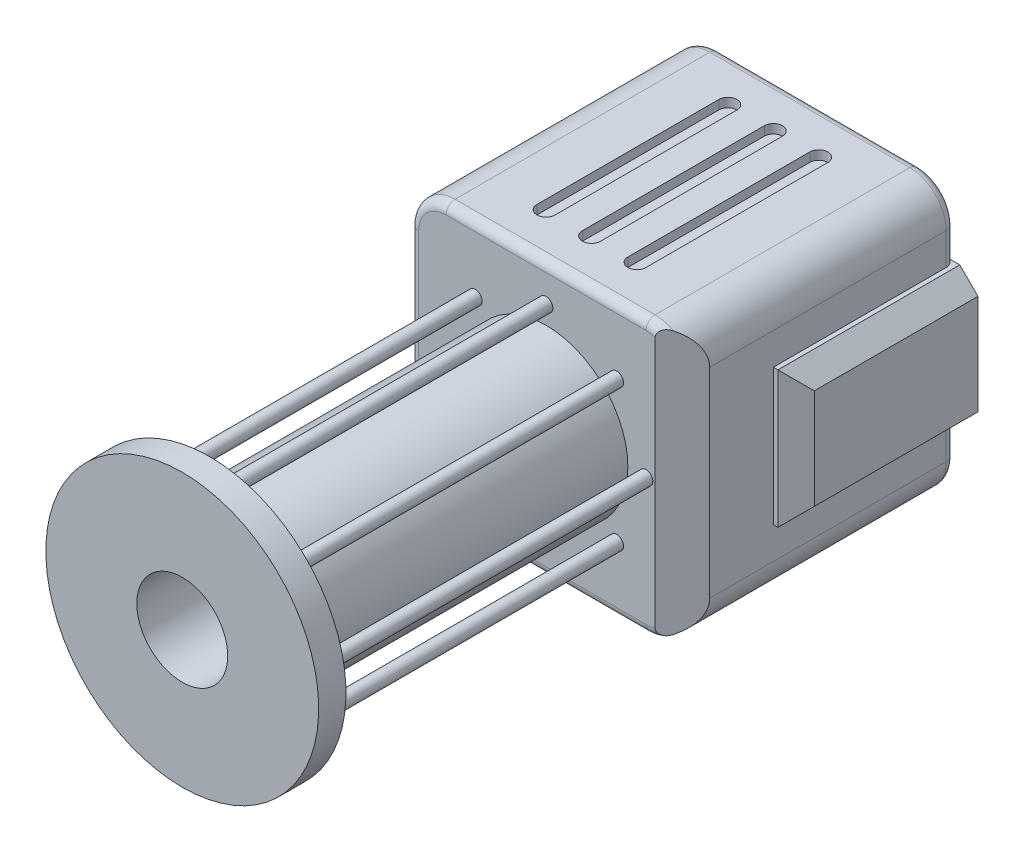
SolidWorks part; units mm, degrees
ref_plane "Front Plane" through (0, 0, 0) normal (0, 0, 1) x (1, 0, 0)
ref_plane "Top Plane" through (0, 0, 0) normal (0, 1, 0) x (1, 0, 0)
ref_plane "Right Plane" through (0, 0, 0) normal (1, 0, 0) x (0, 0, -1)
sketch "Sketch1" plane through (0, 0, 0) normal (0, 0, 1) x (1, 0, 0)
  line L1 (-15, 15) -> (15, 15)
  line L2 (-15, 15) -> (-15, -15)
  line L3 (-15, -15) -> (15, -15)
  line L4 (15, 15) -> (15, -15)
  line L5 (-15, 15) -> (15, -15) construction
  line L6 (-15, -15) -> (15, 15) construction
  point P0 (0, 0)
  dimension "D1" = 30
  dimension "D2" = 30
extrude "Boss-Extrude1" add sketch "Sketch1" along normal mid plane 30
sketch "Sketch2" plane through (0, 0, 0) normal (1, 0, 0) x (0, 0, -1)
  line L0 (-15, 0) -> (-55, 0) construction
  line L1 (-15, -15) -> (-15, 15) construction
  line L2 (-55, 0) -> (-55, 15)
  line L3 (-55, 15) -> (-52, 15)
  line L4 (-52, 15) -> (-52, 9)
  line L5 (-52, 9) -> (-15, 9)
  line L6 (-15, 9) -> (-15, 0)
  line L7 (-15, 0) -> (-55, 0)
  dimension "D1" = 40
  dimension "D2" = 18
  dimension "D3" = 30
  dimension "D4" = 3
revolve "Revolve1" add sketch "Sketch2" angle 360 about L0
fillet "Fillet1" radius 4 4 edges at (-15, 15, 0) (-15, -15, 0) (15, -15, 0) (15, 15, 0)
chamfer "Chamfer2" distance 3 angle 45 1 edges at (15, 0, 15)
fillet "Fillet2" radius 1 15 edges at (13.8284, 13.8284, -15) (15, 0, -15) (13.8284, -13.8284, -15) (0, -15, -15) (-13.8284, -13.8284, -15) (-15, 0, -15) (-13.8284, 13.8284, -15) (11.504, 14.9681, 15) (11.504, -14.9681, 15) (0, -15, 15) (-13.8284, -13.8284, 15) (-15, 0, 15) (-13.8284, 13.8284, 15) (0, 15, -15) (0, 15, 15)
sketch "Sketch3" plane through (0, 0, -15) normal (0, 0, -1) x (-1, 0, 0)
  circle A0 centre (0, 0) radius 10
  dimension "D1" = 20
extrude "Boss-Extrude2" add sketch "Sketch3" along normal mid plane 5
fillet "Fillet3" radius 5 1 edges at (-10, 0, -17.5)
sketch "Sketch5" plane through (0, 0, -15) normal (0, 0, -1) x (-1, 0, 0)
  line L0 (-15, -11) -> (-15, 11) construction
  line L1 (-12.5, -7.5) -> (-17.5, -7.5)
  line L2 (-12.5, -7.5) -> (-12.5, 7.5)
  line L3 (-12.5, 7.5) -> (-17.5, 7.5)
  line L4 (-17.5, -7.5) -> (-17.5, 7.5)
  line L5 (-12.5, -7.5) -> (-17.5, 7.5) construction
  line L6 (-12.5, 7.5) -> (-17.5, -7.5) construction
  point P0 (-15, 0)
  dimension "D1" = 15
  dimension "D2" = 5
extrude "Boss-Extrude3" add sketch "Sketch5" against normal blind 20
chamfer "Chamfer3" distance 2 angle 45 3 edges at (17.5, -7.5, -5) (17.5, 7.5, -5) (17.5, 0, 5)
sketch "Sketch6" plane through (0, 0, 55) normal (0, 0, 1) x (1, 0, 0)
  circle A0 centre (0, 0) radius 5
  dimension "D1" = 10
extrude "Cut-Extrude1" cut sketch "Sketch6" against normal blind 10 and the other way through all
sketch "Sketch7" plane through (0, 0, 55) normal (0, 0, 1) x (1, 0, 0)
  circle A0 centre (0, 11) radius 0.75
  point P2 (0, 0)
  dimension "D1" = 1.5
  dimension "D2" = 11
extrude "Boss-Extrude4" add sketch "Sketch7" against normal up to surface (40 mm away) up to face at (-0.6535, 0, 15)
pattern_circular "CirPattern1" count 8 over 360 about axis through (0, 0, 0) along (0, 0, 1) of "Boss-Extrude4"
sketch "Sketch8" plane through (-15, 0, 0) normal (-1, 0, 0) x (0, 0, 1)
  circle A0 centre (0, 0) radius 5
  dimension "D1" = 10
extrude "Cut-Extrude2" cut sketch "Sketch8" against normal blind 10
sketch "Sketch9" plane through (0, 15, 0) normal (0, 1, 0) x (1, 0, 0)
  line L0 (0, 10) -> (0, -10) construction
  line L1 (1, 10) -> (1, -10)
  line L2 (-1, 10) -> (-1, -10)
  arc A0 (1, 10) -> (-1, 10) centre (0, 10) ccw
  arc A1 (-1, -10) -> (1, -10) centre (0, -10) ccw
  point P2 (0, 0)
  dimension "D1" = 20
  dimension "D2" = 2
extrude "Cut-Extrude3" cut sketch "Sketch9" against normal blind 1
pattern_linear "LPattern1" count 2 spacing 5 along (1, 0, 0) count 2 spacing 5 along (-1, 0, 0) of "Cut-Extrude3"
